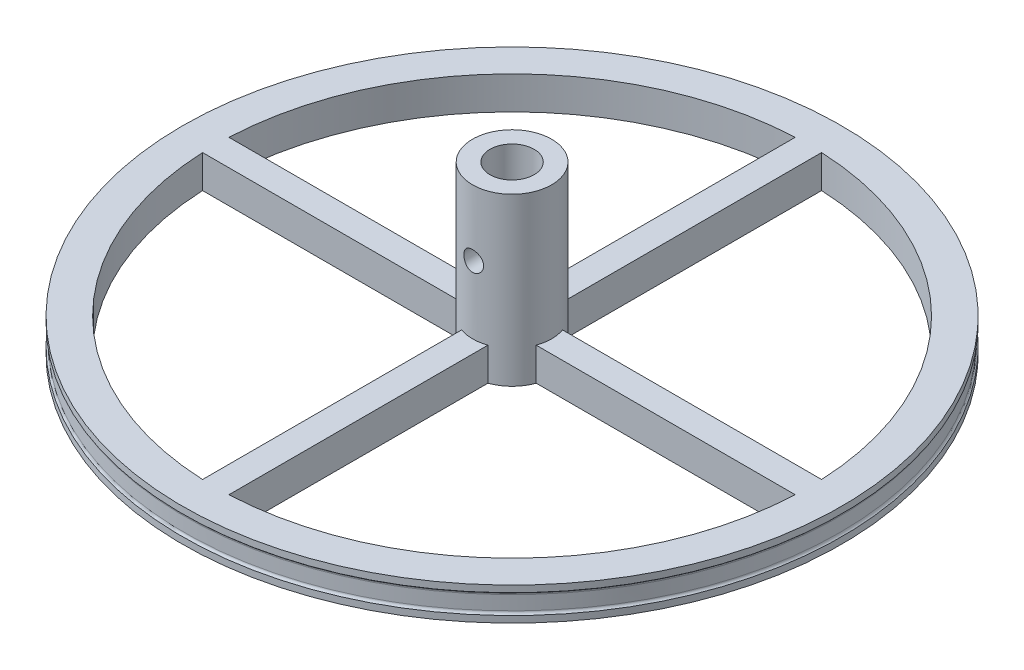
SolidWorks part; units mm, degrees
ref_plane "Front Plane" through (0, 0, 0) normal (0, 0, 1) x (1, 0, 0)
ref_plane "Top Plane" through (0, 0, 0) normal (0, 1, 0) x (1, 0, 0)
ref_plane "Right Plane" through (0, 0, 0) normal (1, 0, 0) x (0, 0, -1)
sketch "Sketch1" plane through (0, 0, 0) normal (0, 0, 1) x (1, 0, 0)
  line L0 (0, 2.2639) -> (0, -2.7361)
  line L1 (0, -2.7361) -> (50, -2.7361)
  line L2 (50, -2.7361) -> (50, -1.7361)
  line L3 (50, -1.7361) -> (49.75, -1.7361)
  line L4 (49.75, -1.7361) -> (49.75, 1.2639)
  line L5 (49.75, 1.2639) -> (50, 1.2639)
  line L6 (50, 1.2639) -> (50, 2.2639)
  line L7 (50, 2.2639) -> (0, 2.2639)
  dimension "D1" = 3
  dimension "D2" = 1
  dimension "D3" = 1
  dimension "D4" = 50
  dimension "D5" = 49.75
  dimension "D6" = 0.25
revolve "Revolve1" add sketch "Sketch1" angle 90 about L0
sketch "Sketch2" plane through (0, 0, 0) normal (0, 1, 0) x (1, 0, 0)
  line L0 (0, -50) -> (0, 0) construction
  line L1 (50, 0) -> (0, 0) construction
  line L2 (0, 0) -> (6, 0)
  line L3 (0, 0) -> (0, -6)
  arc A0 (0, -6) -> (6, 0) centre (0, 0) ccw
  dimension "D1" = 6
extrude "Boss-Extrude2" add sketch "Sketch2" along normal blind 22.5
sketch "Sketch6" plane through (0, 2.2639, 0) normal (0, 1, 0) x (1, 0, 0)
  line L0 (0, -50) -> (0, -6) construction
  line L1 (50, 0) -> (6, 0) construction
  line L2 (2, -5.6569) -> (2, -44.9555)
  line L3 (5.6569, -2) -> (44.9555, -2)
  arc A0 (2, -5.6569) -> (5.6569, -2) centre (0, 0) ccw
  arc A1 (2, -44.9555) -> (44.9555, -2) centre (0, 0) ccw
  dimension "D1" = 6
  dimension "D2" = 45
  dimension "D3" = 2
  dimension "D4" = 2
extrude "Cut-Extrude1" cut sketch "Sketch6" against normal through all
mirror "Mirror3" about plane through (0, 0, 0) normal (0, 0, 1) of "Cut-Extrude1", "Boss-Extrude2", "Revolve1"
mirror "Mirror4" about plane through (0, 0, 0) normal (1, 0, 0) of "Cut-Extrude1", "Mirror3", "Boss-Extrude2", "Revolve1"
sketch "Sketch7" plane through (0, 22.5, 0) normal (0, 1, 0) x (1, 0, 0)
  line L0 (0, 5.643) -> (0, -5.8158) construction
  line L1 (-6.3281, 0) -> (5.497, 0) construction
  circle A0 centre (0, 0) radius 3.35
  dimension "D1" = 6.7
extrude "Cut-Extrude2" cut sketch "Sketch7" against normal blind 20
fillet "Fillet9" radius 0.5 2 edges at (-49.75, -1.7361, 0) (-49.75, 1.2639, 0)
sketch "Sketch8" plane through (0, 0, 0) normal (0, 0, 1) x (1, 0, 0)
  line L0 (0, 14.3969) -> (0, -2.2124) construction
  line L1 (6, 22.5) -> (-6, 22.5) construction
  circle A0 centre (0, 12.5) radius 1.5
  dimension "D1" = 3
  dimension "D2" = 10
extrude "Cut-Extrude3" cut sketch "Sketch8" against normal up to next and the other way up to next
